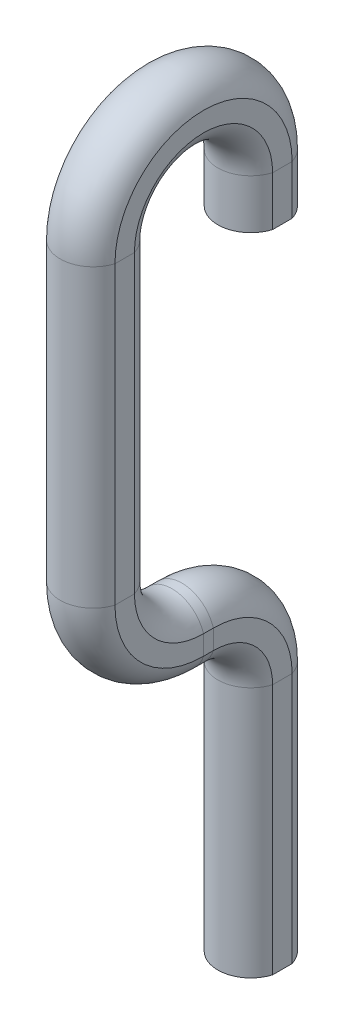
SolidWorks part; units mm, degrees
ref_plane "Front Plane" through (0, 0, 0) normal (1, 0, 0) x (0, 1, 0)
ref_plane "Top Plane" through (0, 0, 0) normal (0, 0, 1) x (0, 1, 0)
ref_plane "Right Plane" through (0, 0, 0) normal (0, 1, 0) x (-1, 0, 0)
sketch "Sketch1" plane through (0, 0, 0) normal (1, 0, 0) x (0, 1, 0)
  line L0 (0, 0) -> (64.77, 0)
  line L1 (82.55, 17.78) -> (82.55, 20.32)
  line L2 (102.87, 40.64) -> (179.07, 40.64)
  line L3 (179.07, 0) -> (166.37, 0)
  arc A0 (64.77, 0) -> (82.55, 17.78) centre (64.77, 17.78) ccw
  arc A1 (82.55, 20.32) -> (102.87, 40.64) centre (102.87, 20.32) cw
  arc A2 (179.07, 40.64) -> (179.07, 0) centre (179.07, 20.32) cw
  dimension "D1" = 20.32
  dimension "D3" = 17.78
  dimension "D4" = 20.32
  dimension "D2" = 82.55
  dimension "D5" = 40.64
  dimension "D6" = 76.2
  dimension "D7" = 12.7
sketch "Sketch2" plane through (0, 0, 0) normal (0, 1, 0) x (-1, 0, 0)
  line L0 (-8.128, 2.5146) -> (-8.128, -2.5146)
  line L1 (0, 17.78) -> (0, 0) construction
  line L2 (0, 17.78) -> (0, 0) construction
  line L3 (8.128, 2.5146) -> (8.128, -2.5146)
  line L4 (-8.128, 0) -> (0, 0) construction
  arc A1 (8.128, 2.5146) -> (-8.128, 2.5146) centre (0, -0.0031) ccw
  arc A2 (8.128, -2.5146) -> (-8.128, -2.5146) centre (0, 0.0031) cw
  point P9 (-7.9262, 2.5146)
  dimension "D2" = 16.256
  dimension "D3" = 8.509
  dimension "D1" = 5.0292
sweep "Sweep1" add profiles "Sketch2" path "Sketch1"
sketch "Sketch3" plane through (0, 0, 0) normal (1, 0, 0) x (0, 1, 0)
  line L0 (0, 8.5059) -> (0, 0)
  line L1 (0, 0) -> (-6.35, 0)
  line L2 (-6.35, 0) -> (-6.35, -5.3286) construction
  line L3 (166.37, -2.5146) -> (166.37, 2.5146) construction
  line L4 (179.07, 8.5059) -> (166.37, 8.5059) construction
  line L5 (166.37, -4.1941) -> (166.37, 8.5059)
  line L6 (166.37, 8.5059) -> (179.07, 8.5059)
  arc A0 (0, 8.5059) -> (-6.35, 0) centre (2.5219, 0) ccw
  arc A1 (179.07, 8.5059) -> (166.37, -4.1941) centre (166.37, 8.5059) cw
  dimension "D1" = 6.35
  dimension "D2" = 12.7
